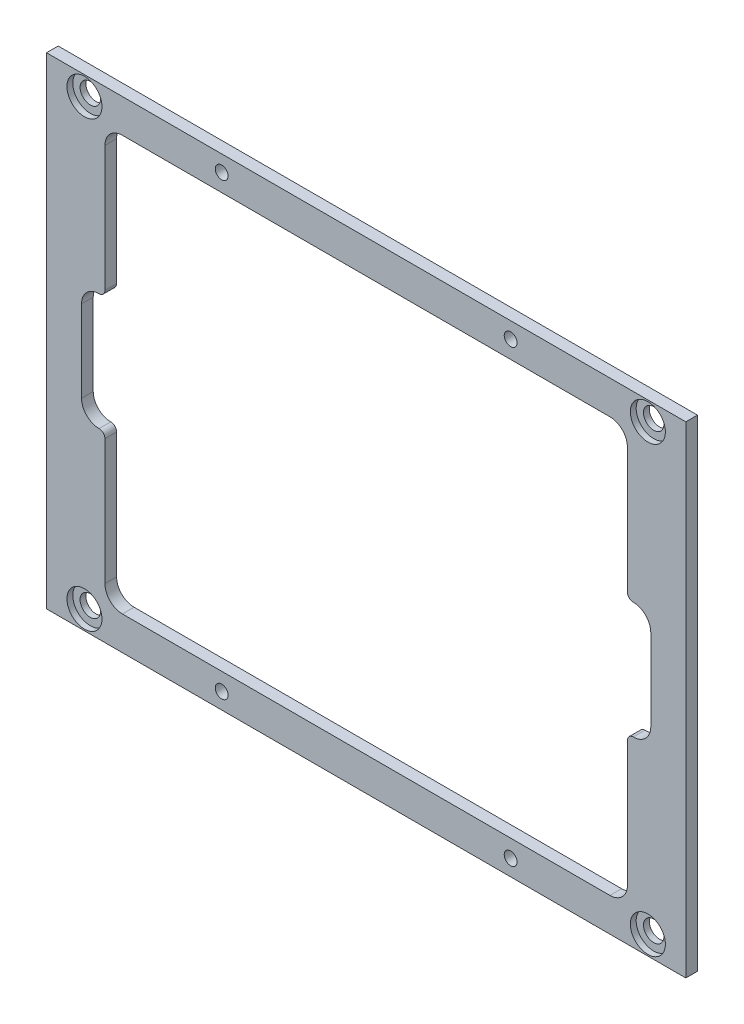
SolidWorks part; units mm, degrees
ref_plane "Front Plane" through (0, 0, 0) normal (0, 0, 1) x (1, 0, 0)
ref_plane "Top Plane" through (0, 0, 0) normal (0, 1, 0) x (1, 0, 0)
ref_plane "Right Plane" through (0, 0, 0) normal (1, 0, 0) x (0, 0, -1)
sketch "Sketch1" plane through (0, 0, 7.4347) normal (0, 0, 1) x (1, 0, 0)
  line L0 (44.0064, 54.7019) -> (48.0064, 54.7019)
  line L1 (-55.4936, 3.4519) -> (54.0064, 3.4519)
  line L2 (-55.4936, 3.4519) -> (-55.4936, 85.9519)
  line L3 (-55.4936, 85.9519) -> (54.0064, 85.9519)
  line L4 (54.0064, 3.4519) -> (54.0064, 85.9519)
  line L5 (55.0064, 3.4519) -> (-56.4936, 3.4519) construction
  line L6 (48.0064, 54.7019) -> (48.0064, 34.7019)
  line L7 (-42.4936, 80.2019) -> (41.0064, 80.2019)
  line L8 (-45.4936, 77.2019) -> (-45.4936, 54.7019)
  line L9 (-42.4936, 9.2019) -> (41.0064, 9.2019)
  line L10 (44.0064, 77.2019) -> (44.0064, 54.7019)
  line L11 (-55.4936, 44.7019) -> (-49.4936, 44.7019) construction
  line L12 (-49.4936, 44.7019) -> (-49.4936, 54.7019)
  line L13 (-45.4936, 34.7019) -> (-49.4936, 34.7019)
  line L14 (54.0064, 44.7019) -> (-55.4936, 44.7019) construction
  line L15 (-45.4936, 54.7019) -> (-49.4936, 54.7019)
  line L16 (-49.4936, 34.7019) -> (-49.4936, 44.7019)
  line L17 (-45.4936, 34.7019) -> (-45.4936, 12.2019)
  line L18 (48.0064, 34.7019) -> (44.0064, 34.7019)
  line L19 (44.0064, 34.7019) -> (44.0064, 12.2019)
  arc A0 (-45.4936, 12.2019) -> (-42.4936, 9.2019) centre (-42.4936, 12.2019) ccw
  arc A1 (41.0064, 9.2019) -> (44.0064, 12.2019) centre (41.0064, 12.2019) ccw
  arc A2 (41.0064, 80.2019) -> (44.0064, 77.2019) centre (41.0064, 77.2019) cw
  arc A3 (-42.4936, 80.2019) -> (-45.4936, 77.2019) centre (-42.4936, 77.2019) ccw
  dimension "D7" = 3
  dimension "D1" = 109.5
  dimension "D2" = 82.5
  dimension "D3" = 10
  dimension "D4" = 35.5
  dimension "D5" = 89.5
  dimension "D6" = 35.5
  dimension "D8" = 4
  dimension "D9" = 10
  dimension "D10" = 10
  dimension "D11" = 10
  dimension "D12" = 10
  dimension "D13" = 4
extrude "Boss-Extrude1" add sketch "Sketch1" along normal blind 2
hole_wizard "Ø3.5 (3.5) Diameter Hole1" positions "Sketch7" profile "Sketch6" hole size "Ø3.5" standard "Ansi Metric" end condition up to next
sketch "Sketch7" plane through (0, 0, 9.4347) normal (0, 0, 1) x (1, 0, 0)
  line L1 (-55.4936, 85.9519) -> (-55.4936, 3.4519) construction
  line L3 (54.0064, 3.4519) -> (54.0064, 85.9519) construction
  line L4 (-55.4936, 44.7019) -> (54.0064, 44.7019) construction
  point P0 (-48.9936, 6.7019)
  point P7 (-48.9936, 82.7019)
  point P9 (47.5064, 82.7019)
  point P11 (47.5064, 6.7019)
  dimension "D1" = 38
  dimension "D2" = 6.5
  dimension "D3" = 6.5
  dimension "D4" = 38
  dimension "D5" = 38
  dimension "D6" = 6.5
  dimension "D7" = 6.5
  dimension "D8" = 38
sketch "Sketch6" plane through (-48.9936, 6.7019, 9.4347) normal (1, 0, 0) x (0, -1, 0)
  line L0 (0, 0) -> (0, 2)
  line L1 (0, 2) -> (1.75, 2)
  line L2 (1.75, 2) -> (1.75, 0)
  line L5 (1.75, 0) -> (0, 0)
  line L11 (0, -6.35) -> (0, 107.95) construction
  dimension "Thru Hole Dia." = 3.5
  dimension "Thru Hole Depth" = 2
hole_wizard "Ø2.2 (2.2) Diameter Hole1" positions "3DSketch4" profile "Sketch11" hole size "Ø2.2" standard "Ansi Metric" end condition up to next
sketch3d "3DSketch4"
  line L1 (-55.4936, 85.9519, 9.4347) -> (-55.4936, 3.4519, 9.4347) construction
  line L2 (54.0064, 3.4519, 9.4347) -> (54.0064, 85.9519, 9.4347) construction
  line L4 (54.0064, 44.7019, 9.4347) -> (-55.4936, 44.7019, 9.4347) construction
  point P0 (-25.4936, 83.2019, 9.4347)
  point P2 (24.0064, 83.2019, 9.4347)
  point P4 (24.0064, 6.2019, 9.4347)
  point P6 (-25.4936, 6.2019, 9.4347)
  dimension "D1" = 38.5
  dimension "D2" = 30
  dimension "D3" = 38.5
  dimension "D4" = 30
  dimension "D5" = 38.5
  dimension "D6" = 30
  dimension "D7" = 38.5
  dimension "D8" = 30
sketch "Sketch11" plane through (-25.4936, 83.2019, 9.4347) normal (1, 0, 0) x (0, -1, 0)
  line L0 (0, 0) -> (0, 2)
  line L1 (0, 2) -> (1.1, 2)
  line L2 (1.1, 2) -> (1.1, 0)
  line L5 (1.1, 0) -> (0, 0)
  line L11 (0, -6.35) -> (0, 107.95) construction
  dimension "Thru Hole Dia." = 2.2
  dimension "Thru Hole Depth" = 2
sketch "Sketch12" plane through (0, 0, 9.4347) normal (0, 0, 1) x (1, 0, 0)
  circle A0 centre (-48.9936, 82.7019) radius 3
  circle A1 centre (47.5064, 82.7019) radius 3
  circle A2 centre (47.5064, 6.7019) radius 3
  circle A3 centre (-48.9936, 6.7019) radius 3
  dimension "D1" = 6
  dimension "D2" = 6
  dimension "D3" = 6
  dimension "D4" = 6
extrude "Cut-Extrude1" cut sketch "Sketch12" against normal blind 1
fillet "Fillet1" radius 3 4 edges at (-49.4936, 34.7019, 8.4347) (-49.4936, 54.7019, 8.4347) (48.0064, 34.7019, 8.4347) (48.0064, 54.7019, 8.4347)
fillet "Fillet2" radius 1 4 edges at (-45.4936, 54.7019, 8.4347) (-45.4936, 34.7019, 8.4347) (44.0064, 34.7019, 8.4347) (44.0064, 54.7019, 8.4347)
